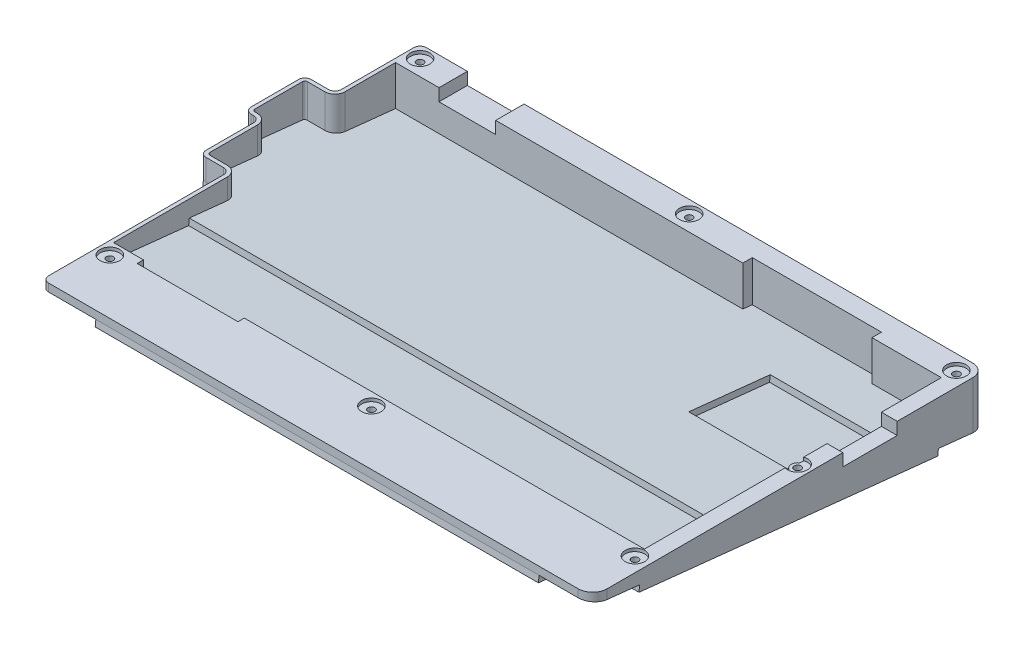
SolidWorks part; units mm, degrees
ref_plane "Front Plane" through (0, 0, 0) normal (0, 0, 1) x (1, 0, 0)
ref_plane "Top Plane" through (0, 0, 0) normal (0, 1, 0) x (1, 0, 0)
ref_plane "Right Plane" through (0, 0, 0) normal (1, 0, 0) x (0, 0, -1)
sketch "Sketch1" plane through (0, 0, 0) normal (0, 1, 0) x (1, 0, 0)
  line L0 (138.4196, 31.7518) -> (125.4196, 31.7518)
  line L1 (-35.0204, 31.7518) -> (107.4196, 31.7518)
  line L2 (140.4196, 29.7518) -> (140.4196, 6.7018)
  line L3 (-34.0204, 3.7518) -> (-34.0204, 22.7518)
  line L4 (136.4596, 27.7518) -> (136.4396, 27.7518)
  line L5 (142.4196, 4.7018) -> (147.9496, 4.7018)
  line L6 (-34.0204, 22.7518) -> (-12.0204, 22.7518)
  line L8 (149.9496, 2.7018) -> (149.9496, -12.3482)
  line L11 (147.9496, -14.3482) -> (147.1896, -14.3482)
  line L14 (145.1896, -16.3482) -> (145.1896, -31.3982)
  line L17 (143.1896, -33.3982) -> (137.6696, -33.3982)
  line L20 (135.6696, -35.3982) -> (135.6696, -77.4982)
  line L21 (-34.0204, -25.6003) -> (-34.0204, -71.4982)
  line L23 (133.6696, -79.4982) -> (-35.0204, -79.4982)
  line L28 (-39.0204, 27.7518) -> (-39.0204, 3.7518)
  line L31 (-34.0204, 3.7518) -> (-39.0204, 3.7518)
  line L32 (-34.0204, -13.4982) -> (-39.0204, -13.4982)
  line L33 (-39.0204, -75.4982) -> (-39.0204, -13.4982)
  line L34 (-34.0204, -71.4982) -> (92.9796, -71.4982)
  line L35 (92.9796, -71.4982) -> (92.9796, -73.4982)
  line L36 (92.9796, -73.4982) -> (124.9796, -73.4982)
  line L37 (124.9796, -73.4982) -> (124.9796, -71.4982)
  line L39 (134.4706, -35.3982) -> (134.4706, -71.4982)
  line L40 (134.4706, -71.4982) -> (124.9796, -71.4982)
  line L41 (137.6696, -32.1992) -> (143.1896, -32.1992)
  line L42 (-34.0204, -13.4982) -> (-34.0204, -22.1362)
  line L43 (143.9906, -31.3982) -> (143.9906, -16.3482)
  line L44 (-12.0204, 22.7518) -> (-12.0204, 25.7518)
  line L45 (147.1896, -13.1492) -> (147.9496, -13.1492)
  line L46 (148.7506, -12.3482) -> (148.7506, 2.7018)
  line L47 (-12.0204, 25.7518) -> (28.9796, 25.7518)
  line L48 (28.9796, 25.7518) -> (28.9796, 22.7518)
  line L49 (28.9796, 22.7518) -> (107.4196, 22.7518)
  line L50 (147.9496, 3.5027) -> (142.4196, 3.5027)
  line L51 (107.4196, 22.7518) -> (107.4196, 31.7518)
  line L52 (139.2206, 6.7018) -> (139.2206, 22.7518)
  line L53 (125.4196, 31.7518) -> (125.4196, 22.7518)
  line L54 (139.2206, 22.7518) -> (125.4196, 22.7518)
  arc A0 (138.4196, 31.7518) -> (140.4196, 29.7518) centre (138.4196, 29.7518) cw
  arc A1 (140.4196, 6.7018) -> (142.4196, 4.7018) centre (142.4196, 6.7018) ccw
  arc A2 (149.9496, 2.7018) -> (147.9496, 4.7018) centre (147.9496, 2.7018) ccw
  arc A3 (149.9496, -12.3482) -> (147.9496, -14.3482) centre (147.9496, -12.3482) cw
  arc A4 (147.1896, -14.3482) -> (145.1896, -16.3482) centre (147.1896, -16.3482) ccw
  arc A5 (145.1896, -31.3982) -> (143.1896, -33.3982) centre (143.1896, -31.3982) cw
  arc A6 (-35.0204, 31.7518) -> (-39.0204, 27.7518) centre (-35.0204, 27.7518) ccw
  arc A7 (-39.0204, -75.4982) -> (-35.0204, -79.4982) centre (-35.0204, -75.4982) ccw
  arc A8 (133.6696, -79.4982) -> (135.6696, -77.4982) centre (133.6696, -77.4982) ccw
  arc A9 (135.6696, -35.3982) -> (137.6696, -33.3982) centre (137.6696, -35.3982) cw
  circle A10 centre (-34.4204, 27.1518) radius 1.1
  circle A11 centre (51.0096, 27.7518) radius 1.1
  circle A12 centre (136.4396, 27.7518) radius 1.1
  circle A13 centre (-34.4204, -74.8982) radius 1.1
  circle A14 centre (48.6296, -75.4982) radius 1.1
  circle A15 centre (131.6496, -75.4982) radius 1.1
  circle A16 centre (-35.0204, -23.8682) radius 1.1
  arc A27 (-34.0204, -22.1362) -> (-34.0204, -25.6003) centre (-35.0204, -23.8682) cw
  arc A28 (139.2206, 6.7018) -> (142.4196, 3.5027) centre (142.4196, 6.7018) ccw
  arc A29 (147.9496, 3.5027) -> (148.7506, 2.7018) centre (147.9496, 2.7018) cw
  arc A30 (148.7506, -12.3482) -> (147.9496, -13.1492) centre (147.9496, -12.3482) cw
  arc A31 (147.1896, -13.1492) -> (143.9906, -16.3482) centre (147.1896, -16.3482) ccw
  arc A32 (143.9906, -31.3982) -> (143.1896, -32.1992) centre (143.1896, -31.3982) cw
  arc A33 (137.6696, -32.1992) -> (134.4706, -35.3982) centre (137.6696, -35.3982) ccw
extrude "Boss-Extrude2" add sketch "Sketch1" against normal blind 4.7 contours L41 A33 L39 L40 L37 L36 L35 L34 L21 A27 L42 L32 L33 A7 L23 A8 L20 A9 L17 A5 L14 A4 L11 A3 L8 A2 L5 A1 L2 A0 L0 L53 L54 L52 A28 L50 A29 L46 A30 L45 A31 L43 A32 A12 A13 A14 A15 | L1 A6 L28 L31 L3 L6 L44 L47 L48 L49 L51 A11 A10 region at (138.2833, 0, -29.6154) region at (31.7683, 0, -26.4895)
move or copy body "Body-Move/Copy1" bodies to move or copy 105 104 copy no rotation origin (55.4646, -2.35, 0) rotation axis (0, 0, 1) rotation angle 180
sketch "Sketch3" plane through (149.9496, 0, 0) normal (1, 0, 0) x (0, 0, -1)
  line L0 (-79.4982, 0) -> (-79.4982, -4.7) construction
  line L1 (-79.4982, 0) -> (-79.4982, -4.7)
  line L2 (31.7518, 0) -> (31.7518, -4.7) construction
  line L3 (31.7518, 0) -> (31.7518, -4.7)
  line L5 (-79.4982, -4.7) -> (31.7518, -16.3928)
  line L6 (31.7518, -16.3928) -> (31.7518, -4.7)
  line L7 (31.7518, -4.7) -> (-79.4982, -4.7)
  line M3 (-75.4982, -4.7) -> (-13.4982, -4.7)
  dimension "D1" = 6
extrude "Boss-Extrude3" add sketch "Sketch3" against normal up to surface (188.97 mm away) contours L6 L7 L5 M3 region at (149.9496, -8.5976, 5.3315) up to face at (-39.0204, -2.35, 4.8232)
sketch "Sketch4" plane through (0, -4.7, 0) normal (0, 1, 0) x (1, 0, 0)
  line L2 (145.9496, -79.4982) -> (149.9496, -79.4982)
  line L3 (149.9496, -79.4982) -> (149.9496, -75.4982)
  line L4 (-29.4904, 6.7018) -> (-29.4904, 29.7518)
  line L5 (-27.4904, 31.7518) -> (-39.0204, 31.7518)
  line L6 (-36.2604, -14.3482) -> (-37.0204, -14.3482)
  line L7 (-39.0204, -12.3482) -> (-39.0204, -79.4982)
  line L8 (-39.0204, -79.4982) -> (-22.7404, -79.4982)
  line L9 (-24.7404, -77.4982) -> (-24.7404, -35.3982)
  line L10 (-26.7404, -33.3982) -> (-32.2604, -33.3982)
  line L11 (-34.2604, -31.3982) -> (-34.2604, -16.3482)
  line L12 (-36.2604, -14.3482) -> (-37.0204, -14.3482)
  line L13 (-39.0204, -12.3482) -> (-39.0204, -79.4982)
  line L14 (-39.0204, -79.4982) -> (-22.7404, -79.4982)
  line L15 (-24.7404, -77.4982) -> (-24.7404, -35.3982)
  line L16 (-26.7404, -33.3982) -> (-32.2604, -33.3982)
  line L17 (-34.2604, -31.3982) -> (-34.2604, -16.3482)
  line L18 (-39.0204, 31.7518) -> (-39.0204, 2.7018)
  line L19 (-37.0204, 4.7018) -> (-31.4904, 4.7018)
  line L20 (-29.4904, 6.7018) -> (-29.4904, 29.7518)
  line L21 (-27.4904, 31.7518) -> (-39.0204, 31.7518)
  line L22 (-39.0204, 31.7518) -> (-39.0204, 2.7018)
  line L23 (-37.0204, 4.7018) -> (-31.4904, 4.7018)
  line L24 (145.9496, -79.4982) -> (149.9496, -79.4982)
  line L25 (149.9496, -79.4982) -> (149.9496, -75.4982)
  line L26 (149.9496, 31.7518) -> (145.9496, 31.7518)
  line L27 (149.9496, 27.7518) -> (149.9496, 31.7518)
  line L28 (149.9496, 31.7518) -> (145.9496, 31.7518)
  line L29 (149.9496, 27.7518) -> (149.9496, 31.7518)
  arc A1 (145.9496, -79.4982) -> (149.9496, -75.4982) centre (145.9496, -75.4982) ccw
  arc A2 (145.9496, -79.4982) -> (149.9496, -75.4982) centre (145.9496, -75.4982) ccw
  arc A3 (-27.4904, 31.7518) -> (-29.4904, 29.7518) centre (-27.4904, 29.7518) ccw
  arc A4 (-37.0204, 4.7018) -> (-39.0204, 2.7018) centre (-37.0204, 2.7018) ccw
  arc A5 (-39.0204, -12.3482) -> (-37.0204, -14.3482) centre (-37.0204, -12.3482) ccw
  arc A6 (-24.7404, -77.4982) -> (-22.7404, -79.4982) centre (-22.7404, -77.4982) ccw
  arc A7 (-24.7404, -35.3982) -> (-26.7404, -33.3982) centre (-26.7404, -35.3982) ccw
  arc A8 (-34.2604, -31.3982) -> (-32.2604, -33.3982) centre (-32.2604, -31.3982) ccw
  arc A9 (-34.2604, -16.3482) -> (-36.2604, -14.3482) centre (-36.2604, -16.3482) ccw
  arc A10 (-39.0204, -12.3482) -> (-37.0204, -14.3482) centre (-37.0204, -12.3482) ccw
  arc A11 (-24.7404, -77.4982) -> (-22.7404, -79.4982) centre (-22.7404, -77.4982) ccw
  arc A12 (-24.7404, -35.3982) -> (-26.7404, -33.3982) centre (-26.7404, -35.3982) ccw
  arc A13 (-34.2604, -31.3982) -> (-32.2604, -33.3982) centre (-32.2604, -31.3982) ccw
  arc A14 (-34.2604, -16.3482) -> (-36.2604, -14.3482) centre (-36.2604, -16.3482) ccw
  arc A15 (-31.4904, 4.7018) -> (-29.4904, 6.7018) centre (-31.4904, 6.7018) ccw
  arc A16 (-27.4904, 31.7518) -> (-29.4904, 29.7518) centre (-27.4904, 29.7518) ccw
  arc A17 (-37.0204, 4.7018) -> (-39.0204, 2.7018) centre (-37.0204, 2.7018) ccw
  arc A18 (-31.4904, 4.7018) -> (-29.4904, 6.7018) centre (-31.4904, 6.7018) ccw
  arc A19 (149.9496, 27.7518) -> (145.9496, 31.7518) centre (145.9496, 27.7518) ccw
  arc A20 (149.9496, 27.7518) -> (145.9496, 31.7518) centre (145.9496, 27.7518) ccw
  dimension "D1" = 0
  dimension "D2" = 0
  dimension "D3" = 0
  dimension "D4" = 0
extrude "Cut-Extrude1" cut sketch "Sketch4" against normal through all
ref_plane "Plane4" through (0, 15, 0) normal (0, 1, 0) x (1, 0, 0)
sketch "Sketch10" plane through (0, 15, 0) normal (0, 1, 0) x (1, 0, 0)
  line L0 (-14.4904, 22.7518) -> (3.5096, 22.7518)
  line L1 (144.9496, 3.7518) -> (144.9496, -13.4982)
  line L27 (-14.4904, 31.7518) -> (-14.4904, 22.7518)
  line L28 (-14.4904, 22.7518) -> (-28.2913, 22.7518)
  line L29 (-28.2913, 22.7518) -> (-28.2913, 6.7018)
  line L30 (-31.4904, 3.5027) -> (-37.0204, 3.5027)
  line L31 (-37.8213, 2.7018) -> (-37.8213, -12.3482)
  line L32 (-37.0204, -13.1492) -> (-36.2604, -13.1492)
  line L33 (-33.0613, -16.3482) -> (-33.0613, -31.3982)
  line L34 (-32.2604, -32.1992) -> (-26.7404, -32.1992)
  line L35 (-23.5413, -35.3982) -> (-23.5413, -71.4982)
  line L36 (-23.5413, -71.4982) -> (-14.0504, -71.4982)
  line L37 (-14.0504, -71.4982) -> (-14.0504, -73.4982)
  line L38 (-14.0504, -73.4982) -> (17.9496, -73.4982)
  line L39 (17.9496, -73.4982) -> (17.9496, -71.4982)
  line L40 (17.9496, -71.4982) -> (144.9496, -71.4982)
  line L41 (144.9496, -71.4982) -> (144.9496, -25.6003)
  line L42 (144.9496, -22.1362) -> (144.9496, -13.4982)
  line L43 (144.9496, -13.4982) -> (149.9496, -13.4982)
  line L44 (149.9496, -13.4982) -> (149.9496, 3.7518)
  line L45 (149.9496, 3.7518) -> (144.9496, 3.7518)
  line L46 (144.9496, 3.7518) -> (144.9496, 22.7518)
  line L47 (144.9496, 22.7518) -> (122.9496, 22.7518)
  line L48 (122.9496, 22.7518) -> (122.9496, 25.7518)
  line L49 (122.9496, 25.7518) -> (81.9496, 25.7518)
  line L50 (81.9496, 25.7518) -> (81.9496, 22.7518)
  line L51 (81.9496, 22.7518) -> (3.5096, 22.7518)
  line L52 (3.5096, 22.7518) -> (3.5096, 31.7518)
  line L53 (3.5096, 31.7518) -> (-14.4904, 31.7518)
  line L54 (-14.4904, 31.7518) -> (-14.4904, 22.7518)
  line L55 (-14.4904, 22.7518) -> (-28.2913, 22.7518)
  line L56 (-28.2913, 22.7518) -> (-28.2913, 6.7018)
  line L57 (-31.4904, 3.5027) -> (-37.0204, 3.5027)
  line L58 (-37.8213, 2.7018) -> (-37.8213, -12.3482)
  line L59 (-37.0204, -13.1492) -> (-36.2604, -13.1492)
  line L60 (-33.0613, -16.3482) -> (-33.0613, -31.3982)
  line L61 (-32.2604, -32.1992) -> (-26.7404, -32.1992)
  line L62 (-23.5413, -35.3982) -> (-23.5413, -71.4982)
  line L63 (-23.5413, -71.4982) -> (-14.0504, -71.4982)
  line L64 (-14.0504, -71.4982) -> (-14.0504, -73.4982)
  line L65 (-14.0504, -73.4982) -> (17.9496, -73.4982)
  line L66 (17.9496, -73.4982) -> (17.9496, -71.4982)
  line L67 (17.9496, -71.4982) -> (144.9496, -71.4982)
  line L68 (144.9496, -71.4982) -> (144.9496, -25.6003)
  line L69 (144.9496, -22.1362) -> (144.9496, -13.4982)
  line L70 (144.9496, -13.4982) -> (149.9496, -13.4982)
  line L71 (149.9496, -13.4982) -> (149.9496, 3.7518)
  line L72 (149.9496, 3.7518) -> (144.9496, 3.7518)
  line L73 (144.9496, 3.7518) -> (144.9496, 22.7518)
  line L74 (144.9496, 22.7518) -> (122.9496, 22.7518)
  line L75 (122.9496, 22.7518) -> (122.9496, 25.7518)
  line L76 (122.9496, 25.7518) -> (81.9496, 25.7518)
  line L77 (81.9496, 25.7518) -> (81.9496, 22.7518)
  line L78 (81.9496, 22.7518) -> (3.5096, 22.7518)
  line L79 (3.5096, 22.7518) -> (3.5096, 31.7518)
  line L80 (3.5096, 31.7518) -> (-14.4904, 31.7518)
  arc A7 (-31.4904, 3.5027) -> (-28.2913, 6.7018) centre (-31.4904, 6.7018) ccw
  arc A8 (-37.0204, 3.5027) -> (-37.8213, 2.7018) centre (-37.0204, 2.7018) ccw
  arc A9 (-37.8213, -12.3482) -> (-37.0204, -13.1492) centre (-37.0204, -12.3482) ccw
  arc A10 (-33.0613, -16.3482) -> (-36.2604, -13.1492) centre (-36.2604, -16.3482) ccw
  arc A11 (-33.0613, -31.3982) -> (-32.2604, -32.1992) centre (-32.2604, -31.3982) ccw
  arc A12 (-23.5413, -35.3982) -> (-26.7404, -32.1992) centre (-26.7404, -35.3982) ccw
  arc A13 (144.9496, -22.1362) -> (144.9496, -25.6003) centre (145.9496, -23.8682) ccw
  arc A14 (-31.4904, 3.5027) -> (-28.2913, 6.7018) centre (-31.4904, 6.7018) ccw
  arc A15 (-37.0204, 3.5027) -> (-37.8213, 2.7018) centre (-37.0204, 2.7018) ccw
  arc A16 (-37.8213, -12.3482) -> (-37.0204, -13.1492) centre (-37.0204, -12.3482) ccw
  arc A17 (-33.0613, -16.3482) -> (-36.2604, -13.1492) centre (-36.2604, -16.3482) ccw
  arc A18 (-33.0613, -31.3982) -> (-32.2604, -32.1992) centre (-32.2604, -31.3982) ccw
  arc A19 (-23.5413, -35.3982) -> (-26.7404, -32.1992) centre (-26.7404, -35.3982) ccw
  arc A20 (144.9496, -22.1362) -> (144.9496, -25.6003) centre (145.9496, -23.8682) ccw
  dimension "D1" = 0
extrude "Cut-Extrude2" cut sketch "Sketch10" against normal through all contours A20 L69 L1 L73 L74 L75 L76 L77 L78 L0 L55 L56 A14 L57 A15 L58 A16 L59 A17 L60 A18 L61 A19 L62 L63 L64 L65 L66 L67 L68 region at (57.9798, 15, 23.6888)
sketch "Sketch11" plane through (144.9496, 0, 0) normal (-1, 0, 0) x (0, 0, 1)
  line L0 (-22.7518, -15.4469) -> (71.4982, -5.5408)
  line L1 (71.4982, -5.5408) -> (71.4982, -3.5408)
  line L2 (71.4982, 0) -> (71.4982, -5.5408) construction
  line L3 (71.4982, -3.5408) -> (-22.7518, -13.4469)
  line L4 (-22.7518, 0) -> (-22.7518, -15.4469) construction
  line L5 (-22.7518, -13.4469) -> (-22.7518, -15.4469)
  dimension "D1" = 2
  dimension "D2" = 2
extrude "Boss-Extrude4" add sketch "Sketch11" along normal up to surface (182.7709 mm away)
sketch "Sketch12" plane through (0, -10.9348, 1.1493) normal (0, 0.9945, -0.1045) x (1, 0, 0)
  line L0 (-29.4904, 7.8943) -> (-29.4904, 24.0327) construction
  line L1 (-29.4904, 24.0327) -> (-37.8213, 24.0327) construction
  line L2 (-37.8213, 24.0327) -> (-37.8213, 5.715) construction
  line L3 (-37.0204, 5.8833) -> (-31.4904, 5.8833) construction
  line L4 (-36.2604, -13.2716) -> (-37.0204, -13.2716) construction
  line L5 (-37.8213, -13.1033) -> (-37.8213, -70.7364) construction
  line L6 (-37.8213, -70.7364) -> (-24.7404, -70.7364) construction
  line L7 (-24.7404, -70.7364) -> (-24.7404, -34.4376) construction
  line L8 (-26.7404, -32.4266) -> (-32.2604, -32.4266) construction
  line L9 (-34.2604, -30.4155) -> (-34.2604, -15.2826) construction
  line L10 (-29.4904, 7.8943) -> (-29.4904, 24.0327)
  line L11 (-29.4904, 24.0327) -> (-37.8213, 24.0327)
  line L12 (-37.8213, 24.0327) -> (-37.8213, 5.715)
  line L13 (-37.0204, 5.8833) -> (-31.4904, 5.8833)
  line L14 (-36.2604, -13.2716) -> (-37.0204, -13.2716)
  line L15 (-37.8213, -13.1033) -> (-37.8213, -70.7364)
  line L16 (-37.8213, -70.7364) -> (-24.7404, -70.7364)
  line L17 (-24.7404, -70.7364) -> (-24.7404, -34.4376)
  line L18 (-26.7404, -32.4266) -> (-32.2604, -32.4266)
  line L19 (-34.2604, -30.4155) -> (-34.2604, -15.2826)
  line L20 (-37.8213, 24.0327) -> (-37.8213, 25.9101)
  line L21 (-29.4904, 24.0327) -> (-29.4904, 27.1127)
  line L22 (-29.4904, 27.1127) -> (-37.8213, 25.9101)
  ellipse E0 centre (-31.4904, 7.8943) end of major axis (-31.4904, 9.9053) minor radius 2 (-31.4904, 5.8833) -> (-29.4904, 7.8943) ccw construction
  ellipse E1 centre (-37.0204, 3.8723) end of major axis (-37.0204, 5.8833) minor radius 2 (-37.0204, 5.8833) -> (-37.8213, 5.715) ccw construction
  ellipse E2 centre (-37.0204, -11.2606) end of major axis (-37.0204, -9.2496) minor radius 2 (-37.8213, -13.1033) -> (-37.0204, -13.2716) ccw construction
  ellipse E3 centre (-26.7404, -34.4376) end of major axis (-26.7404, -32.4266) minor radius 2 (-24.7404, -34.4376) -> (-26.7404, -32.4266) ccw construction
  ellipse E4 centre (-32.2604, -30.4155) end of major axis (-32.2604, -28.4045) minor radius 2 (-34.2604, -30.4155) -> (-32.2604, -32.4266) ccw construction
  ellipse E5 centre (-36.2604, -15.2826) end of major axis (-36.2604, -13.2716) minor radius 2 (-34.2604, -15.2826) -> (-36.2604, -13.2716) ccw construction
  ellipse E6 centre (-31.4904, 7.8943) end of major axis (-31.4904, 9.9053) minor radius 2 (-31.4904, 5.8833) -> (-29.4904, 7.8943) ccw
  ellipse E7 centre (-37.0204, 3.8723) end of major axis (-37.0204, 5.8833) minor radius 2 (-37.0204, 5.8833) -> (-37.8213, 5.715) ccw
  ellipse E8 centre (-37.0204, -11.2606) end of major axis (-37.0204, -9.2496) minor radius 2 (-37.8213, -13.1033) -> (-37.0204, -13.2716) ccw
  ellipse E9 centre (-26.7404, -34.4376) end of major axis (-26.7404, -32.4266) minor radius 2 (-24.7404, -34.4376) -> (-26.7404, -32.4266) ccw
  ellipse E10 centre (-32.2604, -30.4155) end of major axis (-32.2604, -28.4045) minor radius 2 (-34.2604, -30.4155) -> (-32.2604, -32.4266) ccw
  ellipse E11 centre (-36.2604, -15.2826) end of major axis (-36.2604, -13.2716) minor radius 2 (-34.2604, -15.2826) -> (-36.2604, -13.2716) ccw
sketch "Sketch26" plane through (-37.8213, 0, 0) normal (-1, 0, 0) x (0, 0, 1)
  line L0 (14.1808, -9.5651) -> (-4.5344, -11.5322)
  line L1 (-4.5344, -13.5322) -> (14.1808, -11.5651)
  line L4 (-22.7518, -15.4469) -> (-4.5344, -13.5322)
  line L5 (-4.5344, -13.5322) -> (-4.5344, -11.5322)
  line L6 (-4.5344, -11.5322) -> (-22.7518, -13.4469)
  line L7 (-22.7518, -13.4469) -> (-22.7518, -15.4469)
  line L8 (-22.7518, -15.4469) -> (-4.5344, -13.5322)
  line L9 (-4.5344, -13.5322) -> (-4.5344, -11.5322)
  line L10 (-4.5344, -11.5322) -> (-22.7518, -13.4469)
  line L11 (-22.7518, -13.4469) -> (-22.7518, -15.4469)
  line L12 (14.1808, -9.5651) -> (14.1808, -11.5651)
  line L13 (14.1808, -11.5651) -> (71.4982, -5.5408)
  line L14 (71.4982, -5.5408) -> (71.4982, -3.5408)
  line L15 (71.4982, -3.5408) -> (14.1808, -9.5651)
  line L16 (14.1808, -9.5651) -> (14.1808, -11.5651)
  line L17 (14.1808, -11.5651) -> (71.4982, -5.5408)
  line L18 (71.4982, -5.5408) -> (71.4982, -3.5408)
  line L19 (71.4982, -3.5408) -> (14.1808, -9.5651)
  line M9 (14.1808, -9.5651) -> (14.1808, -11.5651)
  line M10 (14.1808, -11.5651) -> (71.4982, -5.5408)
  line M11 (71.4982, -5.5408) -> (71.4982, -3.5408)
  line M12 (71.4982, -3.5408) -> (14.1808, -9.5651)
  dimension "D1" = 0
  dimension "D2" = 0
extrude "Boss-Extrude10" add sketch "Sketch26" along normal blind 11 contours L10 L11 L8 L9 | L9 L1 L0 M9 | M12 M9 M10 M11 region at (-37.8213, -11.5487, 4.8232) region at (-37.8213, -7.553, 42.8395) region at (-37.8213, -13.4895, -13.6431)
sketch "Sketch28" plane through (0, -10.9348, 1.1493) normal (0, 0.9945, -0.1045) x (1, 0, 0)
  line L0 (-48.8213, 24.0327) -> (-52.7132, 28.3929)
  line L1 (-52.7132, 28.3929) -> (-29.4904, 30.8021)
  line L2 (-29.4904, 30.8021) -> (-29.4904, 24.0327)
  line L10 (-29.4904, 7.8943) -> (-29.4904, 24.0327)
  line L11 (-29.4904, 24.0327) -> (-48.8213, 24.0327)
  line L12 (-48.8213, 24.0327) -> (-48.8213, -70.7364)
  line L13 (-48.8213, -70.7364) -> (-24.7404, -70.7364)
  line L14 (-24.7404, -70.7364) -> (-24.7404, -34.4376)
  line L15 (-26.7404, -32.4266) -> (-32.2604, -32.4266)
  line L16 (-34.2604, -30.4155) -> (-34.2604, -15.2826)
  line L17 (-36.2604, -13.2716) -> (-37.0204, -13.2716)
  line L18 (-39.0204, -11.2606) -> (-39.0204, 3.8723)
  line L19 (-37.0204, 5.8833) -> (-31.4904, 5.8833)
  line L20 (-29.4904, 7.8943) -> (-29.4904, 24.0327)
  line L21 (-29.4904, 24.0327) -> (-48.8213, 24.0327)
  line L22 (-48.8213, 24.0327) -> (-48.8213, -70.7364)
  line L23 (-48.8213, -70.7364) -> (-24.7404, -70.7364)
  line L24 (-24.7404, -70.7364) -> (-24.7404, -34.4376)
  line L25 (-26.7404, -32.4266) -> (-32.2604, -32.4266)
  line L26 (-34.2604, -30.4155) -> (-34.2604, -15.2826)
  line L27 (-36.2604, -13.2716) -> (-37.0204, -13.2716)
  line L28 (-39.0204, -11.2606) -> (-39.0204, 3.8723)
  line L29 (-37.0204, 5.8833) -> (-31.4904, 5.8833)
  ellipse E6 centre (-31.4904, 7.8943) end of major axis (-31.4904, 9.9053) minor radius 2 (-31.4904, 5.8833) -> (-29.4904, 7.8943) ccw
  ellipse E7 centre (-26.7404, -34.4376) end of major axis (-26.7404, -32.4266) minor radius 2 (-24.7404, -34.4376) -> (-26.7404, -32.4266) ccw
  ellipse E8 centre (-32.2604, -30.4155) end of major axis (-32.2604, -28.4045) minor radius 2 (-34.2604, -30.4155) -> (-32.2604, -32.4266) ccw
  ellipse E9 centre (-36.2604, -15.2826) end of major axis (-36.2604, -13.2716) minor radius 2 (-34.2604, -15.2826) -> (-36.2604, -13.2716) ccw
  ellipse E10 centre (-37.0204, -11.2606) end of major axis (-37.0204, -9.2496) minor radius 2 (-39.0204, -11.2606) -> (-37.0204, -13.2716) ccw
  ellipse E11 centre (-37.0204, 3.8723) end of major axis (-37.0204, 5.8833) minor radius 2 (-37.0204, 5.8833) -> (-39.0204, 3.8723) ccw
  ellipse E12 centre (-31.4904, 7.8943) end of major axis (-31.4904, 9.9053) minor radius 2 (-31.4904, 5.8833) -> (-29.4904, 7.8943) ccw
  ellipse E13 centre (-26.7404, -34.4376) end of major axis (-26.7404, -32.4266) minor radius 2 (-24.7404, -34.4376) -> (-26.7404, -32.4266) ccw
  ellipse E14 centre (-32.2604, -30.4155) end of major axis (-32.2604, -28.4045) minor radius 2 (-34.2604, -30.4155) -> (-32.2604, -32.4266) ccw
  ellipse E15 centre (-36.2604, -15.2826) end of major axis (-36.2604, -13.2716) minor radius 2 (-34.2604, -15.2826) -> (-36.2604, -13.2716) ccw
  ellipse E16 centre (-37.0204, -11.2606) end of major axis (-37.0204, -9.2496) minor radius 2 (-39.0204, -11.2606) -> (-37.0204, -13.2716) ccw
  ellipse E17 centre (-37.0204, 3.8723) end of major axis (-37.0204, 5.8833) minor radius 2 (-37.0204, 5.8833) -> (-39.0204, 3.8723) ccw
  ellipse M17 centre (-31.4904, 7.8943) end of major axis (-31.4904, 9.9053) minor radius 2 (-31.4904, 5.8833) -> (-29.4904, 7.8943) ccw
  line M18 (-29.4904, 7.8943) -> (-29.4904, 24.0327)
  line M19 (-29.4904, 24.0327) -> (-48.8213, 24.0327)
  line M20 (-48.8213, 24.0327) -> (-48.8213, -70.7364)
  line M21 (-48.8213, -70.7364) -> (-24.7404, -70.7364)
  line M22 (-24.7404, -70.7364) -> (-24.7404, -34.4376)
  ellipse M23 centre (-26.7404, -34.4376) end of major axis (-26.7404, -32.4266) minor radius 2 (-24.7404, -34.4376) -> (-26.7404, -32.4266) ccw
  line M24 (-26.7404, -32.4266) -> (-32.2604, -32.4266)
  ellipse M25 centre (-32.2604, -30.4155) end of major axis (-32.2604, -28.4045) minor radius 2 (-32.2604, -32.4266) -> (-34.2604, -30.4155) cw
  line M26 (-34.2604, -30.4155) -> (-34.2604, -15.2826)
  ellipse M27 centre (-36.2604, -15.2826) end of major axis (-36.2604, -13.2716) minor radius 2 (-34.2604, -15.2826) -> (-36.2604, -13.2716) ccw
  line M28 (-36.2604, -13.2716) -> (-37.0204, -13.2716)
  ellipse M29 centre (-37.0204, -11.2606) end of major axis (-37.0204, -9.2496) minor radius 2 (-37.0204, -13.2716) -> (-39.0204, -11.2606) cw
  line M30 (-39.0204, -11.2606) -> (-39.0204, 3.8723)
  ellipse M31 centre (-37.0204, 3.8723) end of major axis (-37.0204, 5.8833) minor radius 2 (-39.0204, 3.8723) -> (-37.0204, 5.8833) cw
  line M32 (-37.0204, 5.8833) -> (-31.4904, 5.8833)
  dimension "D1" = 0
extrude "Cut-Extrude8" cut sketch "Sketch28" against normal blind 11 contours M32 M17 M18 M19 M20 M21 M22 M23 M24 M25 M26 M27 M28 M29 M30 M31 | L2 L1 L0 M19 region at (-39.4803, -13.7524, -25.6581) region at (-38.8035, -7.967, 29.3861)
sketch "Sketch30" plane through (122.9496, 0, 0) normal (-1, 0, 0) x (0, 0, 1)
  line L0 (-25.7518, -15.7622) -> (-22.7518, -15.4469)
  line L1 (-22.7518, -15.4469) -> (-22.7518, -13.4469)
  line L2 (-22.7518, -15.4469) -> (-22.7518, -13.4469) construction
  line L3 (-22.7518, -13.4469) -> (-25.7518, -13.7622)
  line L4 (-25.7518, 0) -> (-25.7518, -15.7622) construction
  line L5 (-25.7518, -13.7622) -> (-25.7518, -15.7622)
extrude "Boss-Extrude11" add sketch "Sketch30" along normal up to surface (41 mm away)
sketch "Sketch32" plane through (17.9496, 0, 0) normal (-1, 0, 0) x (0, 0, 1)
  line L0 (73.4982, -5.3306) -> (71.4982, -5.5408)
  line L1 (71.4982, -5.5408) -> (71.4982, -3.5408)
  line L2 (71.4982, -3.5408) -> (73.4982, -3.3306)
  line L3 (73.4982, 0) -> (73.4982, -5.3306) construction
  line L4 (73.4982, -3.3306) -> (73.4982, -5.3306)
  dimension "D1" = 2
extrude "Boss-Extrude14" add sketch "Sketch32" along normal up to surface (32 mm away)
sketch "Sketch35" plane through (0, 0, 0) normal (0, 1, 0) x (1, 0, 0)
  line L0 (149.9496, 3.7518) -> (149.9496, -13.4982)
  line L1 (149.9496, -13.4982) -> (144.9496, -13.4982)
  line L2 (144.9496, -13.4982) -> (144.9496, 3.7518)
  line L3 (144.9496, 3.7518) -> (149.9496, 3.7518)
ref_plane "Plane5" through (149.9496, -5.1204, 75.4982) normal (0, -1, 0) x (-1, 0, 0)
sketch "Sketch47" plane through (0, 0, 0) normal (0, 1, 0) x (1, 0, 0)
  circle A0 centre (145.3496, -74.8982) radius 3.1
  circle A1 centre (62.2996, -75.4982) radius 3.1
  circle A2 centre (-20.7204, -75.4982) radius 3.1
  circle A3 centre (-25.5104, 27.7518) radius 3.1
  circle A4 centre (59.9196, 27.7518) radius 3.1
  circle A5 centre (145.3496, 27.1518) radius 3.1
  circle A6 centre (145.9496, -23.8682) radius 3.1
extrude "Cut-Extrude17" cut sketch "Sketch47" against normal blind 1.8
sketch "Sketch48" plane through (0, 0, 0) normal (0, 1, 0) x (1, 0, 0)
  line L10 (145.9496, 31.7518) -> (3.5096, 31.7518)
  line L11 (3.5096, 31.7518) -> (3.5096, 22.7518)
  line L12 (3.5096, 22.7518) -> (81.9496, 22.7518)
  line L13 (81.9496, 22.7518) -> (81.9496, 25.7518)
  line L14 (81.9496, 25.7518) -> (122.9496, 25.7518)
  line L15 (122.9496, 25.7518) -> (122.9496, 22.7518)
  line L16 (122.9496, 22.7518) -> (144.9496, 22.7518)
  line L17 (144.9496, 22.7518) -> (144.9496, 3.7518)
  line L18 (144.9496, 3.7518) -> (149.9496, 3.7518)
  line L19 (149.9496, 3.7518) -> (149.9496, 27.7518)
  line L20 (145.9496, 31.7518) -> (3.5096, 31.7518)
  line L21 (3.5096, 31.7518) -> (3.5096, 22.7518)
  line L22 (3.5096, 22.7518) -> (81.9496, 22.7518)
  line L23 (81.9496, 22.7518) -> (81.9496, 25.7518)
  line L24 (81.9496, 25.7518) -> (122.9496, 25.7518)
  line L25 (122.9496, 25.7518) -> (122.9496, 22.7518)
  line L26 (122.9496, 22.7518) -> (144.9496, 22.7518)
  line L27 (144.9496, 22.7518) -> (144.9496, 3.7518)
  line L28 (144.9496, 3.7518) -> (149.9496, 3.7518)
  line L29 (149.9496, 3.7518) -> (149.9496, 27.7518)
  line L47 (144.9496, -13.4982) -> (144.9496, -20.9339)
  line L48 (144.9496, -26.8025) -> (144.9496, -71.4982)
  line L49 (144.9496, -71.4982) -> (17.9496, -71.4982)
  line L50 (17.9496, -71.4982) -> (17.9496, -73.4982)
  line L51 (17.9496, -73.4982) -> (-14.0504, -73.4982)
  line L52 (-14.0504, -73.4982) -> (-14.0504, -71.4982)
  line L53 (-14.0504, -71.4982) -> (-23.5413, -71.4982)
  line L54 (-23.5413, -71.4982) -> (-23.5413, -35.3982)
  line L55 (-26.7404, -32.1992) -> (-32.2604, -32.1992)
  line L56 (-33.0613, -31.3982) -> (-33.0613, -16.3482)
  line L57 (-36.2604, -13.1492) -> (-37.0204, -13.1492)
  line L58 (-37.8213, -12.3482) -> (-37.8213, 2.7018)
  line L59 (-37.0204, 3.5027) -> (-31.4904, 3.5027)
  line L60 (-28.2913, 6.7018) -> (-28.2913, 22.7518)
  line L61 (-28.2913, 22.7518) -> (-14.4904, 22.7518)
  line L62 (-14.4904, 22.7518) -> (-14.4904, 31.7518)
  line L63 (-14.4904, 31.7518) -> (-27.4904, 31.7518)
  line L64 (-29.4904, 29.7518) -> (-29.4904, 6.7018)
  line L65 (-31.4904, 4.7018) -> (-37.0204, 4.7018)
  line L66 (-39.0204, 2.7018) -> (-39.0204, -12.3482)
  line L67 (-37.0204, -14.3482) -> (-36.2604, -14.3482)
  line L68 (-34.2604, -16.3482) -> (-34.2604, -31.3982)
  line L69 (-32.2604, -33.3982) -> (-26.7404, -33.3982)
  line L70 (-24.7404, -35.3982) -> (-24.7404, -77.4982)
  line L71 (-22.7404, -79.4982) -> (145.9496, -79.4982)
  line L72 (149.9496, -75.4982) -> (149.9496, -13.4982)
  line L73 (149.9496, -13.4982) -> (144.9496, -13.4982)
  line L74 (144.9496, -13.4982) -> (144.9496, -20.9339)
  line L75 (144.9496, -26.8025) -> (144.9496, -71.4982)
  line L76 (144.9496, -71.4982) -> (17.9496, -71.4982)
  line L77 (17.9496, -71.4982) -> (17.9496, -73.4982)
  line L78 (17.9496, -73.4982) -> (-14.0504, -73.4982)
  line L79 (-14.0504, -73.4982) -> (-14.0504, -71.4982)
  line L80 (-14.0504, -71.4982) -> (-23.5413, -71.4982)
  line L81 (-23.5413, -71.4982) -> (-23.5413, -35.3982)
  line L82 (-26.7404, -32.1992) -> (-32.2604, -32.1992)
  line L83 (-33.0613, -31.3982) -> (-33.0613, -16.3482)
  line L84 (-36.2604, -13.1492) -> (-37.0204, -13.1492)
  line L85 (-37.8213, -12.3482) -> (-37.8213, 2.7018)
  line L86 (-37.0204, 3.5027) -> (-31.4904, 3.5027)
  line L87 (-28.2913, 6.7018) -> (-28.2913, 22.7518)
  line L88 (-28.2913, 22.7518) -> (-14.4904, 22.7518)
  line L89 (-14.4904, 22.7518) -> (-14.4904, 31.7518)
  line L90 (-14.4904, 31.7518) -> (-27.4904, 31.7518)
  line L91 (-29.4904, 29.7518) -> (-29.4904, 6.7018)
  line L92 (-31.4904, 4.7018) -> (-37.0204, 4.7018)
  line L93 (-39.0204, 2.7018) -> (-39.0204, -12.3482)
  line L94 (-37.0204, -14.3482) -> (-36.2604, -14.3482)
  line L95 (-34.2604, -16.3482) -> (-34.2604, -31.3982)
  line L96 (-32.2604, -33.3982) -> (-26.7404, -33.3982)
  line L97 (-24.7404, -35.3982) -> (-24.7404, -77.4982)
  line L98 (-22.7404, -79.4982) -> (145.9496, -79.4982)
  line L99 (149.9496, -75.4982) -> (149.9496, -13.4982)
  line L100 (149.9496, -13.4982) -> (144.9496, -13.4982)
  arc A1 (149.9496, 27.7518) -> (145.9496, 31.7518) centre (145.9496, 27.7518) ccw
  arc A2 (149.9496, 27.7518) -> (145.9496, 31.7518) centre (145.9496, 27.7518) ccw
  arc A18 (144.9496, -26.8025) -> (144.9496, -20.9339) centre (145.9496, -23.8682) ccw
  arc A19 (-23.5413, -35.3982) -> (-26.7404, -32.1992) centre (-26.7404, -35.3982) ccw
  arc A20 (-33.0613, -31.3982) -> (-32.2604, -32.1992) centre (-32.2604, -31.3982) ccw
  arc A21 (-33.0613, -16.3482) -> (-36.2604, -13.1492) centre (-36.2604, -16.3482) ccw
  arc A22 (-37.8213, -12.3482) -> (-37.0204, -13.1492) centre (-37.0204, -12.3482) ccw
  arc A23 (-37.0204, 3.5027) -> (-37.8213, 2.7018) centre (-37.0204, 2.7018) ccw
  arc A24 (-31.4904, 3.5027) -> (-28.2913, 6.7018) centre (-31.4904, 6.7018) ccw
  arc A25 (-27.4904, 31.7518) -> (-29.4904, 29.7518) centre (-27.4904, 29.7518) ccw
  arc A26 (-31.4904, 4.7018) -> (-29.4904, 6.7018) centre (-31.4904, 6.7018) ccw
  arc A27 (-37.0204, 4.7018) -> (-39.0204, 2.7018) centre (-37.0204, 2.7018) ccw
  arc A28 (-39.0204, -12.3482) -> (-37.0204, -14.3482) centre (-37.0204, -12.3482) ccw
  arc A29 (-34.2604, -16.3482) -> (-36.2604, -14.3482) centre (-36.2604, -16.3482) ccw
  arc A30 (-34.2604, -31.3982) -> (-32.2604, -33.3982) centre (-32.2604, -31.3982) ccw
  arc A31 (-24.7404, -35.3982) -> (-26.7404, -33.3982) centre (-26.7404, -35.3982) ccw
  arc A32 (-24.7404, -77.4982) -> (-22.7404, -79.4982) centre (-22.7404, -77.4982) ccw
  arc A33 (145.9496, -79.4982) -> (149.9496, -75.4982) centre (145.9496, -75.4982) ccw
  arc A34 (144.9496, -26.8025) -> (144.9496, -20.9339) centre (145.9496, -23.8682) ccw
  arc A35 (-23.5413, -35.3982) -> (-26.7404, -32.1992) centre (-26.7404, -35.3982) ccw
  arc A36 (-33.0613, -31.3982) -> (-32.2604, -32.1992) centre (-32.2604, -31.3982) ccw
  arc A37 (-33.0613, -16.3482) -> (-36.2604, -13.1492) centre (-36.2604, -16.3482) ccw
  arc A38 (-37.8213, -12.3482) -> (-37.0204, -13.1492) centre (-37.0204, -12.3482) ccw
  arc A39 (-37.0204, 3.5027) -> (-37.8213, 2.7018) centre (-37.0204, 2.7018) ccw
  arc A40 (-31.4904, 3.5027) -> (-28.2913, 6.7018) centre (-31.4904, 6.7018) ccw
  arc A41 (-27.4904, 31.7518) -> (-29.4904, 29.7518) centre (-27.4904, 29.7518) ccw
  arc A42 (-31.4904, 4.7018) -> (-29.4904, 6.7018) centre (-31.4904, 6.7018) ccw
  arc A43 (-37.0204, 4.7018) -> (-39.0204, 2.7018) centre (-37.0204, 2.7018) ccw
  arc A44 (-39.0204, -12.3482) -> (-37.0204, -14.3482) centre (-37.0204, -12.3482) ccw
  arc A45 (-34.2604, -16.3482) -> (-36.2604, -14.3482) centre (-36.2604, -16.3482) ccw
  arc A46 (-34.2604, -31.3982) -> (-32.2604, -33.3982) centre (-32.2604, -31.3982) ccw
  arc A47 (-24.7404, -35.3982) -> (-26.7404, -33.3982) centre (-26.7404, -35.3982) ccw
  arc A48 (-24.7404, -77.4982) -> (-22.7404, -79.4982) centre (-22.7404, -77.4982) ccw
  arc A49 (145.9496, -79.4982) -> (149.9496, -75.4982) centre (145.9496, -75.4982) ccw
  dimension "D1" = 0
  dimension "D2" = 0
extrude "Cut-Extrude18" cut sketch "Sketch48" against normal blind 0.8
sketch "Sketch49" plane through (0, -12.913, 1.3572) normal (0, -0.9945, 0.1045) x (1, 0, 0)
  line L0 (17.9496, 70.7364) -> (144.9496, 70.7364) construction
  line L1 (17.9496, 70.7364) -> (144.9496, 70.7364)
  line L2 (-23.5413, 46.5714) -> (-23.5413, 70.7364)
  line L6 (144.9496, 46.5714) -> (144.9496, 70.7364)
  line L9 (17.9496, 70.7364) -> (-23.5413, 70.7364)
  line L10 (144.9496, 46.5714) -> (-23.5413, 46.5714)
extrude "Cut-Extrude19" cut sketch "Sketch49" against normal blind 10
sketch "Sketch50" plane through (0, -12.913, 1.3572) normal (0, -0.9945, 0.1045) x (1, 0, 0)
  line L5 (105.9496, 17.3552) -> (105.9496, -8.6448)
  line L7 (144.9496, -8.6448) -> (144.9496, 17.3552)
  line L12 (105.9496, -8.6448) -> (144.9496, -8.6448)
  line L13 (105.9496, 17.3552) -> (144.9496, 17.3552)
extrude "Cut-Extrude20" cut sketch "Sketch50" against normal blind 10
sketch "Sketch51" plane through (0, 0, 79.4982) normal (0, 0, 1) x (1, 0, 0)
  line L4 (145.9496, -0.8) -> (-22.7404, -0.8)
  line L5 (-22.7404, -0.8) -> (-22.7404, -4.7)
  line L6 (-22.7404, -4.7) -> (145.9496, -4.7)
  line L7 (145.9496, -4.7) -> (145.9496, -0.8)
  line L8 (145.9496, -0.8) -> (-22.7404, -0.8)
  line L9 (-22.7404, -0.8) -> (-22.7404, -4.7)
  line L10 (-22.7404, -4.7) -> (145.9496, -4.7)
  line L11 (145.9496, -4.7) -> (145.9496, -0.8)
  dimension "D1" = 0
extrude "Boss-Extrude15" add sketch "Sketch51" along normal blind 13.5
sketch "Sketch52" plane through (0, 0, 92.9982) normal (0, 0, 1) x (1, 0, 0)
  line L4 (145.9496, -4.7) -> (145.9496, -0.8)
  line L5 (145.9496, -0.8) -> (-22.7404, -0.8)
  line L6 (-22.7404, -0.8) -> (-22.7404, -4.7)
  line L7 (-22.7404, -4.7) -> (145.9496, -4.7)
  line L8 (145.9496, -4.7) -> (145.9496, -0.8)
  line L9 (145.9496, -0.8) -> (-22.7404, -0.8)
  line L10 (-22.7404, -0.8) -> (-22.7404, -4.7)
  line L11 (-22.7404, -4.7) -> (145.9496, -4.7)
  dimension "D1" = 0
extrude "Cut-Extrude21" cut sketch "Sketch52" against normal blind 13.5
sketch "Sketch53" plane through (149.9496, 0, 0) normal (1, 0, 0) x (0, 0, -1)
  line L0 (-79.4982, -4.7) -> (-92.9243, -3.2889)
  line L1 (-79.4982, -0.8) -> (-92.9243, -0.8)
  line L2 (-92.9243, -0.8) -> (-92.9243, -3.2889)
  line L4 (-75.4982, -5.1204) -> (-75.4982, -0.8)
  line L5 (-75.4982, -0.8) -> (-79.4982, -0.8)
  line L6 (-79.4982, -0.8) -> (-79.4982, -4.7)
  line L7 (-79.4982, -4.7) -> (-75.4982, -5.1204)
  line L8 (-75.4982, -5.1204) -> (-75.4982, -0.8)
  line L9 (-75.4982, -0.8) -> (-79.4982, -0.8)
  line L10 (-79.4982, -0.8) -> (-79.4982, -4.7)
  line L11 (-79.4982, -4.7) -> (-75.4982, -5.1204)
  dimension "D1" = 0
extrude "Boss-Extrude16" add sketch "Sketch53" against normal up to surface (174.69 mm away) contours L10 L1 L2 L0 region at (149.9496, -2.4232, 85.717) up to face at (-24.7404, -4.6317, 52.2798)
sketch "Sketch54" plane through (0, 0, 79.4982) normal (0, 0, -1) x (-1, 0, 0)
  line L0 (22.7404, -4.7) -> (22.7404, -6.6661)
  line L1 (22.7404, -6.6661) -> (24.7404, -6.6661)
  line L2 (24.7404, -6.6661) -> (24.7404, -4.7)
  line L4 (22.7404, -0.8) -> (22.7404, -4.7)
  line L5 (22.7404, -4.7) -> (24.7404, -4.7)
  line L6 (24.7404, -4.7) -> (24.7404, -0.8)
  line L7 (24.7404, -0.8) -> (22.7404, -0.8)
  line L8 (22.7404, -0.8) -> (22.7404, -4.7)
  line L9 (22.7404, -4.7) -> (24.7404, -4.7)
  line L10 (24.7404, -4.7) -> (24.7404, -0.8)
  line L11 (24.7404, -0.8) -> (22.7404, -0.8)
  line M5 (22.7404, -0.8) -> (22.7404, -4.7)
  line M6 (22.7404, -4.7) -> (24.7404, -4.7)
  line M7 (24.7404, -4.7) -> (24.7404, -0.8)
  line M8 (24.7404, -0.8) -> (22.7404, -0.8)
  dimension "D1" = 0
extrude "Boss-Extrude17" add sketch "Sketch54" along normal up to vertex (2 mm away) contours L1 L2 L0 M6 | M8 M5 M6 M7 region at (-23.7404, -5.6831, 79.4982) region at (-23.7404, -2.75, 79.4982) up to point (-24.7404, -4.9102, 77.4982)
sketch "Sketch55" plane through (0, 0, 79.4982) normal (0, 0, -1) x (-1, 0, 0)
  line L0 (-145.9496, -4.7) -> (-145.9496, -7.4461)
  line L1 (-145.9496, -7.4461) -> (-149.9496, -7.4461)
  line L2 (-149.9496, -7.4461) -> (-149.9496, -4.7)
  line L4 (-149.9496, -4.7) -> (-145.9496, -4.7)
  line L5 (-145.9496, -4.7) -> (-145.9496, -0.8)
  line L6 (-145.9496, -0.8) -> (-149.9496, -0.8)
  line L7 (-149.9496, -0.8) -> (-149.9496, -4.7)
  line L8 (-149.9496, -4.7) -> (-145.9496, -4.7)
  line L9 (-145.9496, -4.7) -> (-145.9496, -0.8)
  line L10 (-145.9496, -0.8) -> (-149.9496, -0.8)
  line L11 (-149.9496, -0.8) -> (-149.9496, -4.7)
  line M5 (-149.9496, -4.7) -> (-145.9496, -4.7)
  line M6 (-145.9496, -4.7) -> (-145.9496, -0.8)
  line M7 (-145.9496, -0.8) -> (-149.9496, -0.8)
  line M8 (-149.9496, -0.8) -> (-149.9496, -4.7)
  dimension "D1" = 0
extrude "Boss-Extrude18" add sketch "Sketch55" along normal up to vertex (4 mm away) contours M8 M5 M6 M7 | L2 L1 L0 M5 region at (147.9496, -6.073, 79.4982) region at (147.9496, -2.75, 79.4982) up to point (149.9496, -2.9602, 75.4982)
sketch "Sketch56" plane through (-24.7404, 0, 0) normal (-1, 0, 0) x (0, 0, 1)
  line L0 (77.4982, -4.9102) -> (79.4982, -4.7)
  line L9 (92.9243, -0.8) -> (35.3982, -0.8)
  line L10 (35.3982, -0.8) -> (35.3982, -7.3351)
  line L11 (35.3982, -7.3351) -> (35.6061, -9.3132)
  line L12 (35.6061, -9.3132) -> (77.4982, -4.9102)
  line L13 (77.4982, -4.9102) -> (77.4982, -6.6661)
  line L14 (77.4982, -6.6661) -> (79.4982, -6.6661)
  line L15 (79.4982, -6.6661) -> (79.4982, -4.7)
  line L16 (79.4982, -4.7) -> (92.9243, -3.2889)
  line L17 (92.9243, -3.2889) -> (92.9243, -0.8)
  line L18 (92.9243, -0.8) -> (35.3982, -0.8)
  line L19 (35.3982, -0.8) -> (35.3982, -7.3351)
  line L20 (35.3982, -7.3351) -> (35.6061, -9.3132)
  line L21 (35.6061, -9.3132) -> (77.4982, -4.9102)
  line L22 (77.4982, -4.9102) -> (77.4982, -6.6661)
  line L23 (77.4982, -6.6661) -> (79.4982, -6.6661)
  line L24 (79.4982, -6.6661) -> (79.4982, -4.7)
  line L25 (79.4982, -4.7) -> (92.9243, -3.2889)
  line L26 (92.9243, -3.2889) -> (92.9243, -0.8)
  line M14 (77.4982, -4.9102) -> (77.4982, -6.6661)
  line M15 (77.4982, -6.6661) -> (79.4982, -6.6661)
  line M16 (79.4982, -6.6661) -> (79.4982, -4.7)
  dimension "D1" = 0
extrude "Cut-Extrude22" cut sketch "Sketch56" against normal blind 13.5 and the other way blind 13.5 contours L0 M14 M15 M16 region at (-24.7404, -5.7346, 78.517)
sketch "Sketch57" plane through (149.9496, 0, 0) normal (1, 0, 0) x (0, 0, -1)
  line L0 (-75.4982, -5.1204) -> (-79.4982, -4.7)
  line L12 (-13.4982, -4.7) -> (-13.4982, -0.8)
  line L13 (-13.4982, -0.8) -> (-92.9243, -0.8)
  line L14 (-92.9243, -0.8) -> (-92.9243, -3.2889)
  line L15 (-92.9243, -3.2889) -> (-79.4982, -4.7)
  line L16 (-79.4982, -4.7) -> (-79.4982, -7.4461)
  line L17 (-79.4982, -7.4461) -> (-75.4982, -7.4461)
  line L18 (-75.4982, -7.4461) -> (-75.4982, -5.1204)
  line L19 (-75.4982, -5.1204) -> (27.7518, -15.9724)
  line L20 (27.7518, -15.9724) -> (27.7518, -0.8)
  line L21 (27.7518, -0.8) -> (3.7518, -0.8)
  line L22 (3.7518, -0.8) -> (3.7518, -4.7)
  line L23 (3.7518, -4.7) -> (-13.4982, -4.7)
  line L24 (-13.4982, -4.7) -> (-13.4982, -0.8)
  line L25 (-13.4982, -0.8) -> (-92.9243, -0.8)
  line L26 (-92.9243, -0.8) -> (-92.9243, -3.2889)
  line L27 (-92.9243, -3.2889) -> (-79.4982, -4.7)
  line L28 (-79.4982, -4.7) -> (-79.4982, -7.4461)
  line L29 (-79.4982, -7.4461) -> (-75.4982, -7.4461)
  line L30 (-75.4982, -7.4461) -> (-75.4982, -5.1204)
  line L31 (-75.4982, -5.1204) -> (27.7518, -15.9724)
  line L32 (27.7518, -15.9724) -> (27.7518, -0.8)
  line L33 (27.7518, -0.8) -> (3.7518, -0.8)
  line L34 (3.7518, -0.8) -> (3.7518, -4.7)
  line L35 (3.7518, -4.7) -> (-13.4982, -4.7)
  line M17 (-79.4982, -4.7) -> (-79.4982, -7.4461)
  line M18 (-79.4982, -7.4461) -> (-75.4982, -7.4461)
  line M19 (-75.4982, -7.4461) -> (-75.4982, -5.1204)
  dimension "D1" = 0
extrude "Cut-Extrude23" cut sketch "Sketch57" against normal blind 13.5 and the other way blind 13.5 contours L0 M19 M17 M18 region at (149.9496, -6.1752, 77.5535)
sketch "Sketch58" plane through (0, -1.8, 0) normal (0, 1, 0) x (1, 0, 0)
  circle A0 centre (145.3496, -74.8982) radius 1.1
extrude "Cut-Extrude24" cut sketch "Sketch58" against normal up to surface (2.9 mm away) up to face at (145.544, -4.7, 75.0926)
sketch "Sketch59" plane through (0, -1.8, 0) normal (0, 1, 0) x (1, 0, 0)
  circle A0 centre (145.3496, -74.8982) radius 3.1
extrude "Cut-Extrude25" cut sketch "Sketch59" along normal up to surface (1 mm away) up to face at (145.4259, -0.8, 74.9744)
sketch "Sketch60" plane through (0, -1.8, 0) normal (0, 1, 0) x (1, 0, 0)
  circle A0 centre (-20.7204, -75.4982) radius 3.1
extrude "Cut-Extrude26" cut sketch "Sketch60" along normal up to surface (1 mm away) up to face at (-1.6058, -0.8, 21.8502)
sketch "Sketch61" plane through (0, -0.8, 0) normal (0, 1, 0) x (1, 0, 0)
  line L0 (-24.7404, -92.9243) -> (-24.7404, -90.9243)
  line L1 (-24.7404, -35.3982) -> (-24.7404, -92.9243) construction
  line L2 (-24.7404, -90.9243) -> (-22.7404, -90.9243)
  line L3 (149.9496, -92.9243) -> (149.9496, -88.3243)
  line L4 (149.9496, -92.9243) -> (149.9496, -13.4982) construction
  line L5 (149.9496, -88.3243) -> (145.3496, -88.3243)
  line L6 (-24.7404, -92.9243) -> (149.9496, -92.9243) construction
  arc A0 (149.9496, -88.3243) -> (145.3496, -92.9243) centre (145.3496, -88.3243) cw
  arc A1 (-24.7404, -90.9243) -> (-22.7404, -92.9243) centre (-22.7404, -90.9243) ccw
  line M1 (-24.7404, -92.9243) -> (149.9496, -92.9243)
  line M2 (149.9496, -92.9243) -> (149.9496, -13.4982)
  line M41 (-24.7404, -35.3982) -> (-24.7404, -92.9243)
extrude "Cut-Extrude27" cut sketch "Sketch61" against normal blind 13.5 contours A1 M41 M1 | A0 M2 M1 region at (148.9222, -0.8, 91.8968) region at (-24.2936, -0.8, 92.4775)
sketch "Sketch62" plane through (0, -12.913, 1.3572) normal (0, -0.9945, 0.1045) x (1, 0, 0)
  line L1 (149.9496, 87.4461) -> (149.9496, -29.2693) construction
  line L2 (132.9496, -33.2914) -> (132.9496, -18.2914)
  line L3 (-27.4904, -33.2914) -> (145.9496, -33.2914) construction
  line L4 (132.9496, -18.2914) -> (149.9496, -18.2914)
  line L5 (-29.4904, -31.2803) -> (-29.4904, -7.8943) construction
  line L6 (-12.4904, -33.2914) -> (-12.4904, -18.2914)
  line L7 (-12.4904, -18.2914) -> (-29.4904, -18.2914)
  line L8 (-24.7404, 34.4376) -> (-24.7404, 90.0604) construction
  line L9 (-7.7404, 92.0714) -> (-7.7404, 77.0714)
  line L10 (-22.7404, 92.0714) -> (145.3496, 92.0714) construction
  line L11 (-7.7404, 77.0714) -> (-24.7404, 77.0714)
  line L12 (132.9496, 92.0714) -> (132.9496, 77.0714)
  line L13 (132.9496, 77.0714) -> (149.9496, 77.0714)
  line L23 (145.3496, 92.0714) -> (-22.7404, 92.0714)
  line L24 (-24.7404, 90.0604) -> (-24.7404, 34.4376)
  line L25 (-26.7404, 32.4266) -> (-32.2604, 32.4266)
  line L26 (-34.2604, 30.4155) -> (-34.2604, 15.2826)
  line L27 (-36.2604, 13.2716) -> (-37.0204, 13.2716)
  line L28 (-39.0204, 11.2606) -> (-39.0204, -3.8723)
  line L29 (-37.0204, -5.8833) -> (-31.4904, -5.8833)
  line L30 (-29.4904, -7.8943) -> (-29.4904, -31.2803)
  line L31 (-27.4904, -33.2914) -> (145.9496, -33.2914)
  line L32 (149.9496, -29.2693) -> (149.9496, 87.4461)
  line L33 (145.3496, 92.0714) -> (-22.7404, 92.0714)
  line L34 (-24.7404, 90.0604) -> (-24.7404, 34.4376)
  line L35 (-26.7404, 32.4266) -> (-32.2604, 32.4266)
  line L36 (-34.2604, 30.4155) -> (-34.2604, 15.2826)
  line L37 (-36.2604, 13.2716) -> (-37.0204, 13.2716)
  line L38 (-39.0204, 11.2606) -> (-39.0204, -3.8723)
  line L39 (-37.0204, -5.8833) -> (-31.4904, -5.8833)
  line L40 (-29.4904, -7.8943) -> (-29.4904, -31.2803)
  line L41 (-27.4904, -33.2914) -> (145.9496, -33.2914)
  line L42 (149.9496, -29.2693) -> (149.9496, 87.4461)
  ellipse E10 centre (-22.7404, 90.0604) end of major axis (-22.7404, 92.0714) minor radius 2 (-22.7404, 92.0714) -> (-24.7404, 90.0604) ccw
  ellipse E11 centre (-26.7404, 34.4376) end of major axis (-26.7404, 32.4266) minor radius 2 (-26.7404, 32.4266) -> (-24.7404, 34.4376) ccw
  ellipse E12 centre (-32.2604, 30.4155) end of major axis (-32.2604, 28.4045) minor radius 2 (-32.2604, 32.4266) -> (-34.2604, 30.4155) ccw
  ellipse E13 centre (-36.2604, 15.2826) end of major axis (-36.2604, 13.2716) minor radius 2 (-36.2604, 13.2716) -> (-34.2604, 15.2826) ccw
  ellipse E14 centre (-37.0204, 11.2606) end of major axis (-37.0204, 9.2496) minor radius 2 (-37.0204, 13.2716) -> (-39.0204, 11.2606) ccw
  ellipse E15 centre (-37.0204, -3.8723) end of major axis (-37.0204, -5.8833) minor radius 2 (-39.0204, -3.8723) -> (-37.0204, -5.8833) ccw
  ellipse E16 centre (-31.4904, -7.8943) end of major axis (-31.4904, -9.9053) minor radius 2 (-29.4904, -7.8943) -> (-31.4904, -5.8833) ccw
  ellipse E17 centre (-27.4904, -31.2803) end of major axis (-27.4904, -29.2693) minor radius 2 (-29.4904, -31.2803) -> (-27.4904, -33.2914) ccw
  ellipse E18 centre (145.9496, -29.2693) end of major axis (145.9496, -25.2473) minor radius 4 (145.9496, -33.2914) -> (149.9496, -29.2693) ccw
  ellipse E19 centre (145.3496, 87.4461) end of major axis (145.3496, 92.0714) minor radius 4.6 (149.9496, 87.4461) -> (145.3496, 92.0714) ccw
  ellipse E20 centre (-22.7404, 90.0604) end of major axis (-22.7404, 92.0714) minor radius 2 (-22.7404, 92.0714) -> (-24.7404, 90.0604) ccw
  ellipse E21 centre (-26.7404, 34.4376) end of major axis (-26.7404, 32.4266) minor radius 2 (-26.7404, 32.4266) -> (-24.7404, 34.4376) ccw
  ellipse E22 centre (-32.2604, 30.4155) end of major axis (-32.2604, 28.4045) minor radius 2 (-32.2604, 32.4266) -> (-34.2604, 30.4155) ccw
  ellipse E23 centre (-36.2604, 15.2826) end of major axis (-36.2604, 13.2716) minor radius 2 (-36.2604, 13.2716) -> (-34.2604, 15.2826) ccw
  ellipse E24 centre (-37.0204, 11.2606) end of major axis (-37.0204, 9.2496) minor radius 2 (-37.0204, 13.2716) -> (-39.0204, 11.2606) ccw
  ellipse E25 centre (-37.0204, -3.8723) end of major axis (-37.0204, -5.8833) minor radius 2 (-39.0204, -3.8723) -> (-37.0204, -5.8833) ccw
  ellipse E26 centre (-31.4904, -7.8943) end of major axis (-31.4904, -9.9053) minor radius 2 (-29.4904, -7.8943) -> (-31.4904, -5.8833) ccw
  ellipse E27 centre (-27.4904, -31.2803) end of major axis (-27.4904, -29.2693) minor radius 2 (-29.4904, -31.2803) -> (-27.4904, -33.2914) ccw
  ellipse E28 centre (145.9496, -29.2693) end of major axis (145.9496, -25.2473) minor radius 4 (145.9496, -33.2914) -> (149.9496, -29.2693) ccw
  ellipse E29 centre (145.3496, 87.4461) end of major axis (145.3496, 92.0714) minor radius 4.6 (149.9496, 87.4461) -> (145.3496, 92.0714) ccw
  line M24 (-23.5413, 70.7364) -> (144.9496, 70.7364)
  line M25 (144.9496, 70.7364) -> (144.9496, 46.5714)
  line M26 (144.9496, 46.5714) -> (-23.5413, 46.5714)
  line M27 (-23.5413, 46.5714) -> (-23.5413, 70.7364)
  line M28 (144.9496, -8.6448) -> (105.9496, -8.6448)
  line M29 (105.9496, -8.6448) -> (105.9496, 17.3552)
  line M30 (105.9496, 17.3552) -> (144.9496, 17.3552)
  line M31 (144.9496, 17.3552) -> (144.9496, -8.6448)
  line M32 (145.3496, 92.0714) -> (-22.7404, 92.0714)
  line M34 (-24.7404, 90.0604) -> (-24.7404, 34.4376)
  ellipse M35 centre (-26.7404, 34.4376) end of major axis (-26.7404, 32.4266) minor radius 2 (-24.7404, 34.4376) -> (-26.7404, 32.4266) cw
  line M36 (-26.7404, 32.4266) -> (-32.2604, 32.4266)
  ellipse M37 centre (-32.2604, 30.4155) end of major axis (-32.2604, 28.4045) minor radius 2 (-32.2604, 32.4266) -> (-34.2604, 30.4155) ccw
  line M38 (-34.2604, 30.4155) -> (-34.2604, 15.2826)
  ellipse M39 centre (-36.2604, 15.2826) end of major axis (-36.2604, 13.2716) minor radius 2 (-34.2604, 15.2826) -> (-36.2604, 13.2716) cw
  line M40 (-36.2604, 13.2716) -> (-37.0204, 13.2716)
  ellipse M41 centre (-37.0204, 11.2606) end of major axis (-37.0204, 9.2496) minor radius 2 (-37.0204, 13.2716) -> (-39.0204, 11.2606) ccw
  line M42 (-39.0204, 11.2606) -> (-39.0204, -3.8723)
  ellipse M43 centre (-37.0204, -3.8723) end of major axis (-37.0204, -5.8833) minor radius 2 (-39.0204, -3.8723) -> (-37.0204, -5.8833) ccw
  line M44 (-37.0204, -5.8833) -> (-31.4904, -5.8833)
  ellipse M45 centre (-31.4904, -7.8943) end of major axis (-31.4904, -9.9053) minor radius 2 (-31.4904, -5.8833) -> (-29.4904, -7.8943) cw
  line M46 (-29.4904, -7.8943) -> (-29.4904, -31.2803)
  line M48 (-27.4904, -33.2914) -> (145.9496, -33.2914)
  line M50 (149.9496, -29.2693) -> (149.9496, 87.4461)
  dimension "D1" = 0
extrude "Boss-Extrude20" add sketch "Sketch62" along normal blind 2 contours M28 M31 M30 M29 | L13 L12 L9 L11 L7 L6 L2 L4 M32 M34 M35 M36 M37 M38 M39 M40 M41 M42 M43 M44 M45 M46 M48 M50 M31 M28 M29 M30 M27 M24 M25 M26 | M24 M27 M26 M25 region at (55.9455, -10.5324, 24.007) region at (60.7042, -6.7819, 59.6898) region at (125.4496, -12.4577, 5.6886)
